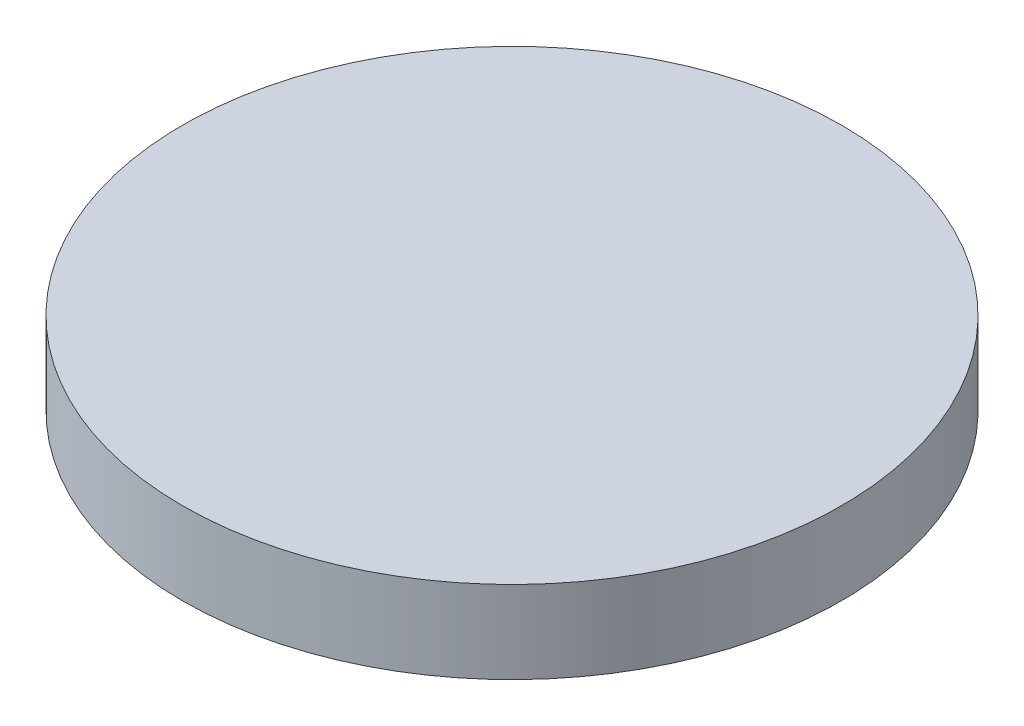
SolidWorks part; units mm, degrees
ref_plane "Płaszczyzna przednia" through (0, 0, 0) normal (0, 0, 1) x (1, 0, 0)
ref_plane "Płaszczyzna górna" through (0, 0, 0) normal (0, 1, 0) x (1, 0, 0)
ref_plane "Płaszczyzna prawa" through (0, 0, 0) normal (1, 0, 0) x (0, 0, -1)
sketch3d "3DSketch1"
  line L0 (0, 0, 0) -> (84.2789, 179.6103, -13.2292)
  line L1 (84.2789, 179.6103, -13.2292) -> (43.8956, 80.9881, 154.6418)
  line L2 (84.2789, 179.6103, -13.2292) -> (172.7178, 12.7631, 49.0474)
  line L3 (84.2789, 179.6103, -13.2292) -> (84.2789, 345.9881, -13.2292)
  circle A0 centre (0, 0, 0) radius 20
  point P7 (0, 20, 0)
  point P8 (82.4979, 228.621, -34.9849)
  point P9 (81.4388, 174.3241, -11.0572)
  point P10 (81.2924, 175.6148, -11.6358)
  point P11 (84.2789, 179.6103, -13.2292)
  dimension "D4" = 40
  dimension "D1" = 180
  dimension "D2" = 180
  dimension "D3" = 180
  dimension "D5" = 265
extrude "Boss-Extrude1" add sketch "3DSketch1" along direction (0, 1, 0) on the side against the normal blind 5 contours A0
